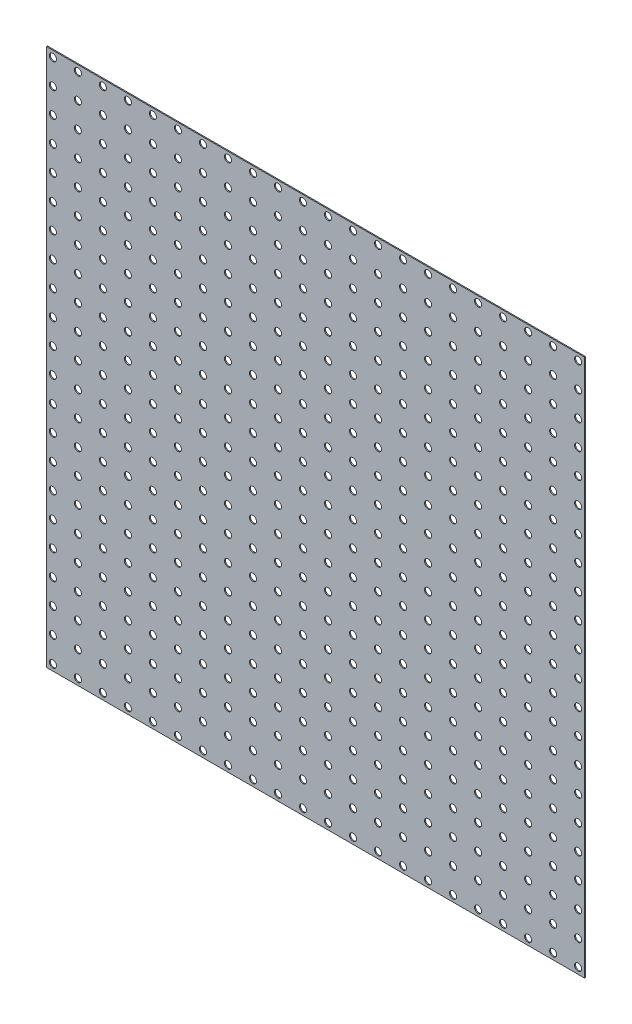
SolidWorks part; units mm, degrees
ref_plane "Front Plane" through (0, 0, 0) normal (0, 0, 1) x (1, 0, 0)
ref_plane "Top Plane" through (0, 0, 0) normal (0, 1, 0) x (1, 0, 0)
ref_plane "Right Plane" through (0, 0, 0) normal (1, 0, 0) x (0, 0, -1)
sketch "Sketch2" plane through (0, 0, 0) normal (0, 0, 1) x (1, 0, 0)
  line L1 (0, 0) -> (546.1, 0)
  line L2 (0, 0) -> (0, 546.1)
  line L3 (0, 546.1) -> (546.1, 546.1)
  line L4 (546.1, 0) -> (546.1, 546.1)
  dimension "D1" = 546.1
  dimension "D2" = 546.1
extrude "Boss-Extrude1" add sketch "Sketch2" along normal blind 1.016
sketch "Sketch3" plane through (0, 0, 1.016) normal (0, 0, 1) x (1, 0, 0)
  line L0 (0, 546.1) -> (0, 0) construction
  line L1 (0, 0) -> (546.1, 0) construction
  circle A0 centre (6.35, 6.35) radius 3.5719
  circle A1 centre (31.75, 6.35) radius 3.5719
  circle A2 centre (31.75, 31.75) radius 3.5719
  circle A3 centre (6.35, 31.75) radius 3.5719
  point P8 (0, 0)
  point P9 (0, 0)
  point P10 (0, 0)
  point P11 (0, 0)
  point P12 (0, 0)
  point P14 (16.1336, 13.9341)
  dimension "D1" = 7.1437
  dimension "D2" = 25.4
  dimension "D3" = 25.4
  dimension "D4" = 6.35
  dimension "D5" = 6.35
extrude "Cut-Extrude1" cut sketch "Sketch3" against normal through all
pattern_linear "LPattern1" count 11 spacing 50.8 along (0, 1, 0) count 11 spacing 50.8 along (1, 0, 0) of "Cut-Extrude1"
